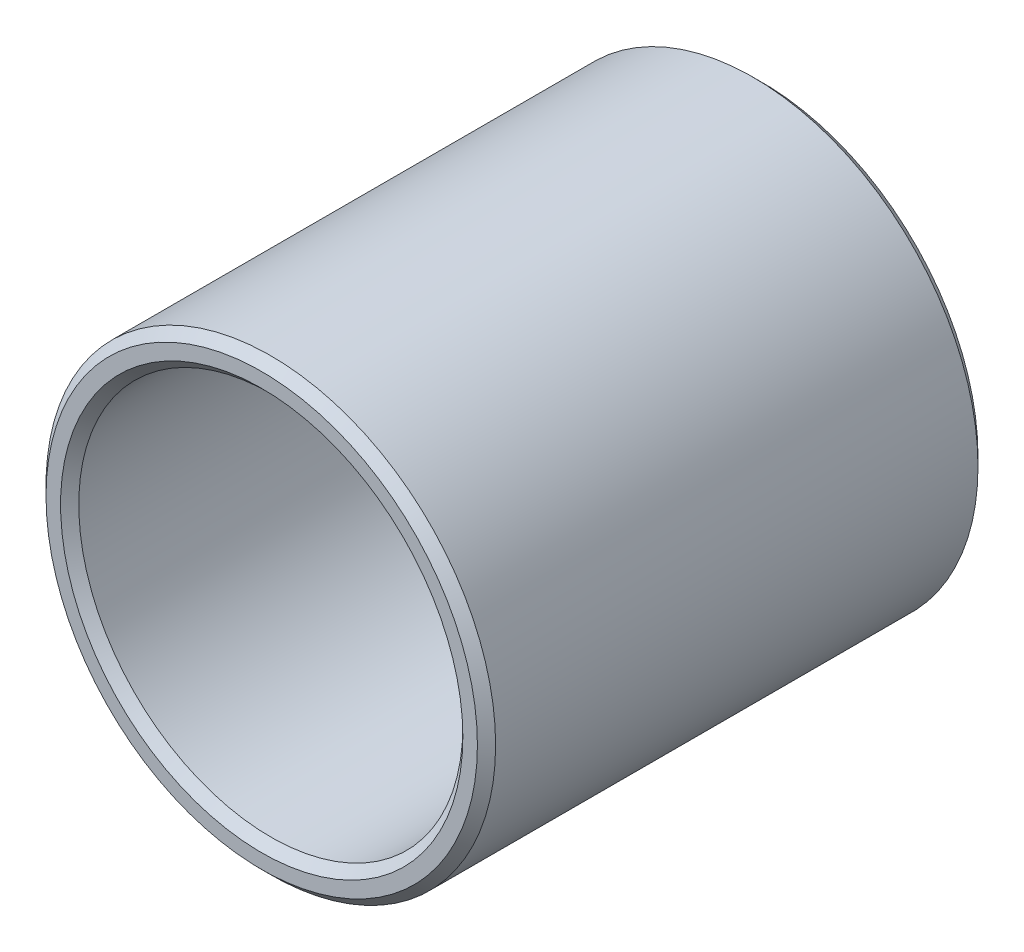
SolidWorks part; units mm, degrees
ref_plane "Ebene vorne" through (0, 0, 0) normal (0, 0, 1) x (1, 0, 0)
ref_plane "Ebene oben" through (0, 0, 0) normal (0, 1, 0) x (1, 0, 0)
ref_plane "Ebene rechts" through (0, 0, 0) normal (1, 0, 0) x (0, 0, -1)
sketch "Skizze1" plane through (0, 0, 0) normal (0, 0, 1) x (1, 0, 0)
  circle A0 centre (0, 0) radius 10.55
  circle A1 centre (0, 0) radius 12.35
  dimension "D1" = 24.7
  dimension "D2" = 21.1
extrude "Aufsatz-Linear austragen1" add sketch "Skizze1" along normal mid plane 27.5
chamfer "Fase1" distance 0.5 angle 45 4 edges at (12.35, 0, -13.75) (12.35, 0, 13.75) (10.55, 0, -13.75) (10.55, 0, 13.75)
ref_axis "Achse1" through (0, 0, 15.125) along (0, 0, -1)
